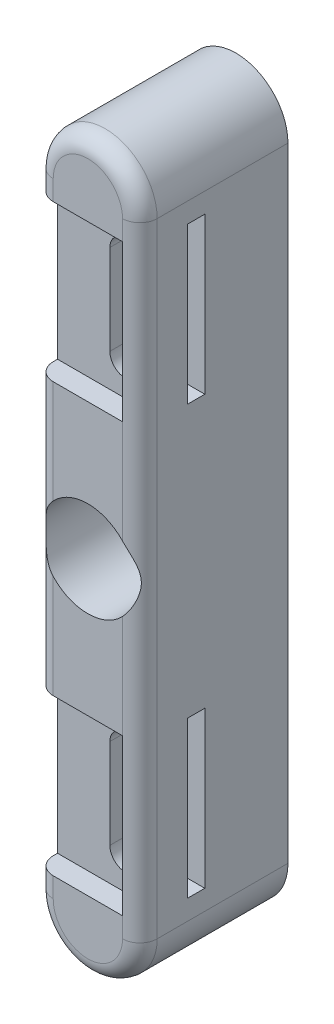
SolidWorks part; units mm, degrees
ref_plane "Alzado" through (0, 0, 0) normal (0, 0, 1) x (1, 0, 0)
ref_plane "Planta" through (0, 0, 0) normal (0, 1, 0) x (1, 0, 0)
ref_plane "Vista lateral" through (0, 0, 0) normal (1, 0, 0) x (0, 0, -1)
sketch "Croquis1" plane through (0, 0, 0) normal (0, 0, 1) x (1, 0, 0)
  line L0 (58.9, -7.25) -> (58.9, 64.75) construction
  line L1 (52.9, -7.25) -> (52.9, 64.75)
  line L2 (64.9, -7.25) -> (64.9, 64.75)
  arc A0 (52.9, -7.25) -> (64.9, -7.25) centre (58.9, -7.25) ccw
  arc A1 (64.9, 64.75) -> (52.9, 64.75) centre (58.9, 64.75) ccw
  arc A2 (64.9, 64.75) -> (58.9, 70.75) centre (58.9, 64.75) ccw construction
  arc A3 (58.9, -13.25) -> (64.9, -7.25) centre (58.9, -7.25) ccw construction
  point P4 (58.9, 28.75)
  dimension "D1" = 6
extrude "Saliente-Extruir1" add sketch "Croquis1" along normal up to surface (17.1 mm away) contours A0 L2 A1 L1
fillet "Redondeo1" radius 2 4 edges at (58.9, 70.75, 17.1) (64.9, 28.75, 17.1) (58.9, -13.25, 17.1) (52.9, 28.75, 17.1)
sketch "Croquis2" plane through (0, 0, 17.1) normal (0, 0, 1) x (1, 0, 0)
  line L0 (46.8348, -4.9448) -> (62.9, -4.9448)
  line L1 (46.8348, -4.9448) -> (46.8348, 13.0552)
  line L2 (62.9, -4.9448) -> (62.9, 13.0552)
  line L3 (46.8348, 13.0552) -> (62.9, 13.0552)
  line L5 (62.9, -7.25) -> (62.9, 64.75) construction
  line L6 (62.9, 28.75) -> (50062.9, 28.75) construction
  line L7 (62.9, 62.4448) -> (62.9, 44.4448)
  line L8 (46.8348, 44.4448) -> (62.9, 44.4448)
  line L9 (46.8348, 62.4448) -> (46.8348, 44.4448)
  line L10 (46.8348, 62.4448) -> (62.9, 62.4448)
  point P8 (62.9, 28.75)
  dimension "D1" = 18
extrude "Cortar-Extruir1" cut sketch "Croquis2" against normal blind 2.5
sketch "Croquis3" plane through (0, 0, 17.1) normal (0, 0, 1) x (1, 0, 0)
  line L0 (58.9, 64.75) -> (58.9, -7.25) construction
  circle A0 centre (58.9, 28.75) radius 5.5
  dimension "D1" = 11
extrude "Cortar-Extruir2" cut sketch "Croquis3" against normal through all contours A0
sketch "Croquis4" plane through (64.9, 0, 0) normal (1, 0, 0) x (0, 0, -1)
  line L0 (-17.1, 62.4448) -> (0, 62.4448) construction
  line L1 (0, 64.75) -> (0, -7.25) construction
  line L2 (-17.1, 44.4448) -> (0, 44.4448) construction
  line L3 (-17.1, 13.0552) -> (0, 13.0552) construction
  line L4 (-17.1, -4.9448) -> (0, -4.9448) construction
  line L5 (-15.1, 28.75) -> (0, 28.75) construction
  line L6 (-15.1, 64.75) -> (-15.1, -7.25) construction
  line L7 (-14.6, -4.9448) -> (-14.6, 13.0552) construction
  line L8 (-11.6, 13.0552) -> (-9.6, 13.0552)
  line L9 (-11.6, 13.0552) -> (-11.6, -4.9448)
  line L10 (-11.6, -4.9448) -> (-9.6, -4.9448)
  line L11 (-9.6, 13.0552) -> (-9.6, -4.9448)
  line L12 (-11.6, 62.4448) -> (-9.6, 62.4448)
  line L13 (-11.6, 44.4448) -> (-9.6, 44.4448)
  line L14 (-9.6, 44.4448) -> (-9.6, 62.4448)
  line L15 (-11.6, 44.4448) -> (-11.6, 62.4448)
  dimension "D1" = 3
  dimension "D2" = 2
extrude "Cortar-Extruir3" cut sketch "Croquis4" against normal blind 6.5
sketch "Croquis5" plane through (0, 0, 14.6) normal (0, 0, 1) x (1, 0, 0)
  line L0 (60.741, 9.2452) -> (60.741, 50009.2452) construction
  line L1 (52.9, 28.75) -> (64.9, 28.75) construction
  line L2 (52.9, 13.0552) -> (52.9, 44.4448) construction
  line L3 (64.9, 64.75) -> (64.9, -7.25) construction
  line L4 (60.741, 9.2452) -> (60.741, -1.1348) construction
  line L5 (62.541, 9.2452) -> (62.541, -1.1348)
  line L6 (58.941, 9.2452) -> (58.941, -1.1348)
  line L7 (62.9, 13.0552) -> (54.9, 13.0552) construction
  line L8 (60.741, 48.2548) -> (60.741, 58.6348) construction
  line L9 (62.541, 48.2548) -> (62.541, 58.6348)
  line L10 (58.941, 48.2548) -> (58.941, 58.6348)
  arc A0 (62.541, 9.2452) -> (58.941, 9.2452) centre (60.741, 9.2452) ccw
  arc A1 (58.941, -1.1348) -> (62.541, -1.1348) centre (60.741, -1.1348) ccw
  arc A2 (62.541, 48.2548) -> (58.941, 48.2548) centre (60.741, 48.2548) cw
  arc A3 (58.941, 58.6348) -> (62.541, 58.6348) centre (60.741, 58.6348) cw
  point P11 (60.741, 4.0552)
  point P25 (60.741, 53.4448)
  dimension "D1" = 1.8
  dimension "D2" = 10.38
  dimension "D3" = 3.81
extrude "Cortar-Extruir4" cut sketch "Croquis5" against normal through all
